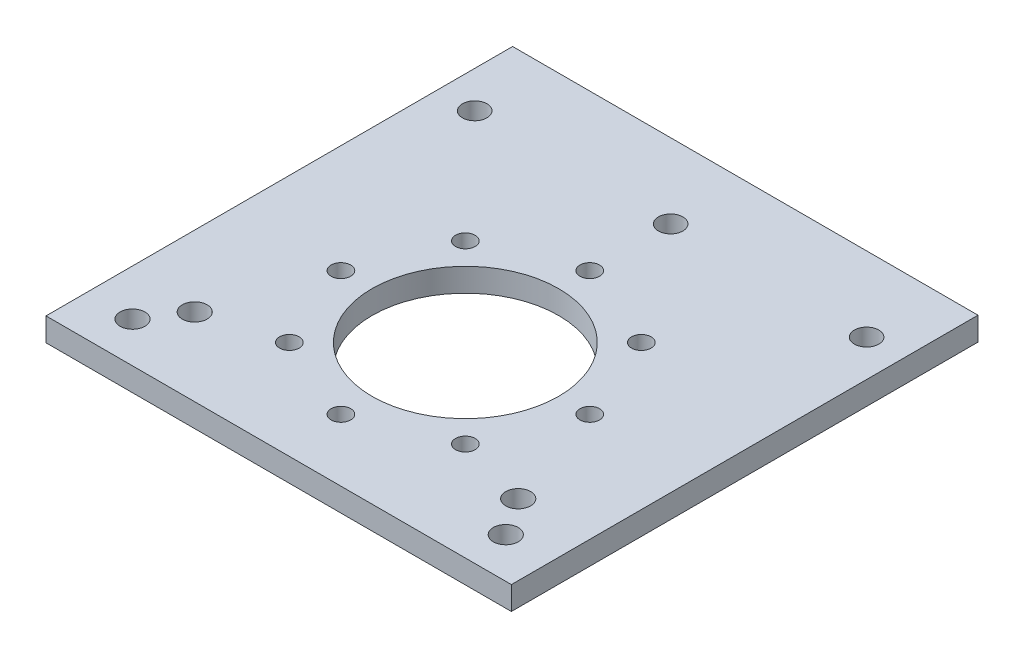
SolidWorks part; units mm, degrees
material "6061 Alloy"
ref_plane "Front Plane" through (0, 0, 0) normal (0, 0, 1) x (1, 0, 0)
ref_plane "Top Plane" through (0, 0, 0) normal (0, 1, 0) x (1, 0, 0)
ref_plane "Right Plane" through (0, 0, 0) normal (1, 0, 0) x (0, 0, -1)
sketch "Sketch2" plane through (0, 0, 0) normal (0, 1, 0) x (1, 0, 0)
  line L0 (0, 0) -> (0, 34.925) construction
  line L1 (-47.5, -60.325) -> (-47.5, 34.925)
  line L2 (47.5, -60.325) -> (47.5, 34.925)
  line L3 (-47.5, 34.925) -> (47.5, 34.925)
  line L4 (-47.5, -60.325) -> (47.5, -60.325)
  point P3 (47.5, -12.7)
  point P5 (0, 34.925)
  point P12 (0, -60.325)
  dimension "D1" = 95.25
  dimension "D2" = 95
  dimension "D3" = 12.7
extrude "Boss-Extrude3" add sketch "Sketch2" along normal blind 4.7625
sketch "Sketch3" plane through (0, 4.7625, 0) normal (0, 1, 0) x (1, 0, 0)
  line L0 (47.5, 34.925) -> (-47.5, 34.925) construction
  circle A1 centre (0, -22.225) radius 19.05
  dimension "D2" = 38.1
  dimension "D3" = 57.15
extrude "Cut-Extrude1" cut sketch "Sketch3" against normal through all
sketch "Sketch4" plane through (0, 4.7625, 0) normal (0, 1, 0) x (1, 0, 0)
  line L0 (47.5, 34.925) -> (-47.5, 34.925) construction
  line L1 (0, 34.925) -> (0, 55.3884) construction
  point P0 (-40, 19.685)
  point P7 (40, 19.685)
  point P8 (0, 19.685)
  point P10 (0, 19.685)
  dimension "D1" = 15.24
  dimension "D2" = 80
hole_wizard "M6x1.0 Tapped Hole1" positions "Sketch4" profile "Sketch6" tap size "M6x1.0" standard "ANSI Metric"
sketch "Sketch6" plane through (-40, 4.7625, -19.685) normal (1, 0, 0) x (0, 0, 1)
  line L0 (0, 0) -> (0, 6.2647)
  line L1 (0, 6.2647) -> (2.5, 4.7625)
  line L2 (2.5, 4.7625) -> (2.5, 0)
  line L5 (2.5, 0) -> (0, 0)
  line L10 (0, 6.2647) -> (-2.5, 4.7625) construction
  line L11 (0, -6.35) -> (0, 107.95) construction
  dimension "Tap Drill Dia." = 5
  dimension "Tap Drill Depth" = 4.7625
  dimension "Drill Angle" = 118
sketch "Sketch7" plane through (0, 4.7625, 0) normal (0, 1, 0) x (1, 0, 0)
  line L0 (0, 0) -> (0, -60.325) construction
  line L1 (-47.5, -60.325) -> (47.5, -60.325) construction
  circle A0 centre (-33.02, -44.45) radius 2.54
  circle A1 centre (33.02, -44.45) radius 2.54
  circle A2 centre (-38.1, -52.07) radius 2.54
  circle A3 centre (38.1, -52.07) radius 2.54
  dimension "D3" = 5.08
  dimension "D4" = 5.08
  dimension "D6" = 38.1
  dimension "D1" = 44.45
  dimension "D2" = 33.02
  dimension "D5" = 7.62
extrude "Cut-Extrude2" cut sketch "Sketch7" against normal blind 7.62
sketch "Sketch12" plane through (0, 4.7625, 0) normal (0, 1, 0) x (1, 0, 0)
  line L0 (47.5, 34.925) -> (-47.5, 34.925) construction
  circle A0 centre (0, -22.225) radius 25.4
  circle A1 centre (0, 3.175) radius 2
  circle A2 centre (17.9605, -4.2645) radius 2
  circle A3 centre (25.4, -22.225) radius 2
  circle A4 centre (17.9605, -40.1855) radius 2
  circle A5 centre (0, -47.625) radius 2
  circle A6 centre (-17.9605, -40.1855) radius 2
  circle A7 centre (-25.4, -22.225) radius 2
  circle A8 centre (-17.9605, -4.2645) radius 2
  point P25 (0, -22.225)
  dimension "D1" = 4
  dimension "D2" = 50.8
  dimension "D3" = 57.15
  dimension "D4" = 8
extrude "Cut-Extrude3" cut sketch "Sketch12" against normal through all contours A8 | A7 | A6 | A5 | A4 | A3 | A2 | A1
